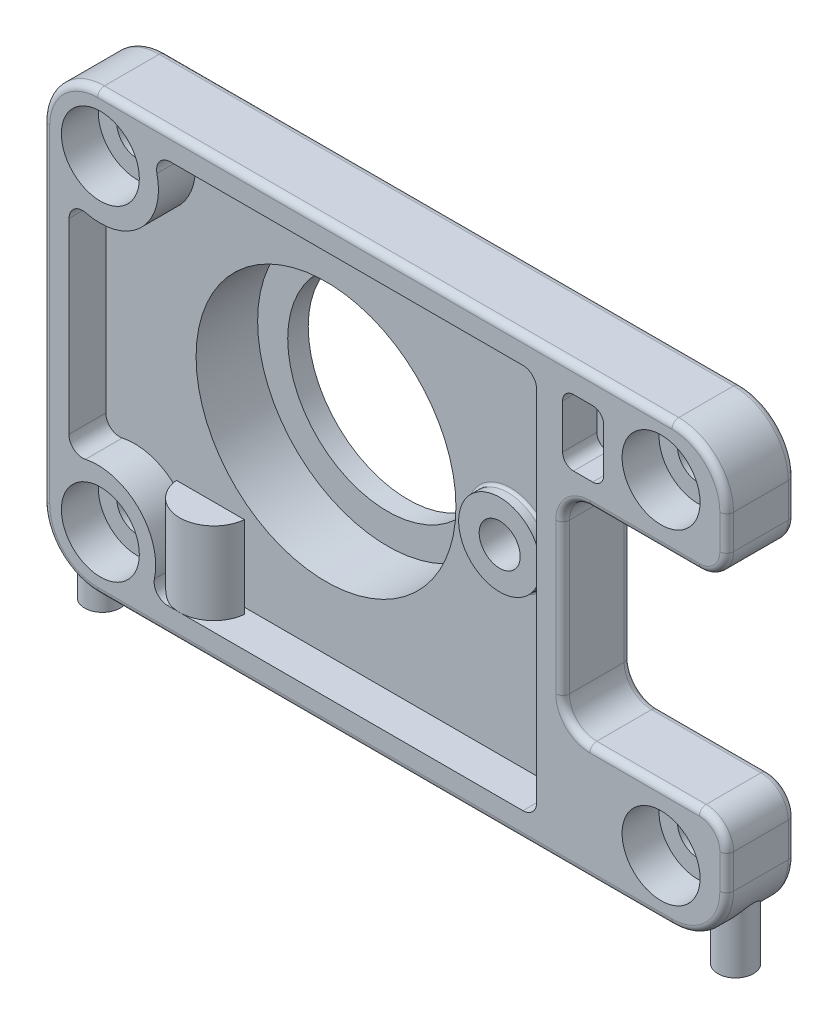
SolidWorks part; units mm, degrees
note: The reader was unsure of these and kept them because the rebuilt part matched: shared geometry of "草图16<2>", "草图16<3>".
ref_plane "前视基准面" through (0, 0, 0) normal (0, 0, 1) x (1, 0, 0)
ref_plane "上视基准面" through (0, 0, 0) normal (0, 1, 0) x (1, 0, 0)
ref_plane "右视基准面" through (0, 0, 0) normal (1, 0, 0) x (0, 0, -1)
sketch "草图1" plane through (0, 0, 0) normal (0, 0, 1) x (1, 0, 0)
  line L0 (0, 16) -> (50, 16) construction
  line L1 (0, 0) -> (50, 0)
  line L2 (0, 0) -> (0, 32)
  line L3 (0, 32) -> (50, 32)
  line L4 (50, 0) -> (50, 8.5)
  line L5 (50, 23.5) -> (38, 23.5)
  line L6 (38, 23.5) -> (38, 8.5)
  line L7 (50, 8.5) -> (38, 8.5)
  line L8 (50, 23.5) -> (50, 32)
  line L9 (4.2, 27.9) -> (5.7, 27.9) construction
  line L10 (4.2, 27.9) -> (46.7, 27.9) construction
  line L11 (4.2, 4.1) -> (50, 4.25) construction
  line L12 (25, 0) -> (25, 37.6238) construction
  circle A0 centre (4.2, 27.9) radius 1.5
  circle A1 centre (45.2, 27.9) radius 1.5
  circle A2 centre (45.2, 4.1) radius 1.5
  circle A3 centre (4.2, 4.1) radius 1.5
  circle A4 centre (18, 16) radius 9.5
  point P22 (38, 16)
  dimension "D3" = 3
  dimension "D10" = 18
  dimension "D11" = 19
  dimension "D1" = 50
  dimension "D2" = 32
  dimension "D6" = 4.2
  dimension "D8" = 23.8
  dimension "D12" = 8.5
  dimension "D13" = 12
  dimension "D14" = 41
  dimension "D4" = 2
  dimension "D5" = 2
extrude "凸台-拉伸1" add sketch "草图1" along normal blind 5
sketch "草图2" plane through (0, 0, 5) normal (0, 0, 1) x (1, 0, 0)
  line L0 (38, 8.5) -> (38, 23.5) construction
  line L1 (38, 25.2613) -> (41, 25.2613)
  line L2 (38, 25.2613) -> (38, 30.1)
  line L3 (36.1, 1.9) -> (36.1, 30.1)
  line L4 (7.6949, 1.9) -> (36.1, 1.9)
  line L5 (36.1, 30.1) -> (7.8363, 30.1)
  line L6 (38, 30.1) -> (41, 30.1)
  line L7 (41, 25.2613) -> (41, 30.1)
  line L8 (38, 6.74) -> (38, 1.9)
  line L9 (38, 1.9) -> (41, 1.9)
  line L10 (41, 1.9) -> (41, 6.74)
  line L11 (41, 6.74) -> (38, 6.74)
  line L24 (1.9124, 24.3182) -> (1.9, 7.6949)
  circle A0 centre (4.2, 27.9) radius 1.5 construction
  circle A1 centre (4.2, 27.9) radius 1.5 construction
  circle A2 centre (4.2, 4.1) radius 1.5 construction
  circle A3 centre (4.2, 4.1) radius 1.5 construction
  circle A4 centre (45.2, 27.9) radius 1.5 construction
  circle A5 centre (45.2, 27.9) radius 1.5 construction
  circle A6 centre (45.2, 4.1) radius 1.5 construction
  circle A7 centre (45.2, 4.1) radius 1.5 construction
  circle A8 centre (4.2, 27.9) radius 2.85
  circle A9 centre (4.2, 4.1) radius 2.85
  circle A10 centre (45.2, 4.1) radius 2.85
  circle A11 centre (45.2, 27.9) radius 2.85
  arc A12 (1.9124, 24.3182) -> (7.8363, 30.1) centre (4.2, 27.9) ccw
  circle A15 centre (4.2, 27.9) radius 4.25 construction
  arc A16 (7.6949, 1.9) -> (1.9, 7.6949) centre (4, 4) ccw
  circle M13 centre (45.2, 4.1) radius 1.5
  circle M14 centre (18, 16) radius 9.5
  circle M23 centre (4.2, 27.9) radius 1.5
  circle M24 centre (45.2, 27.9) radius 1.5
  circle M25 centre (4.2, 4.1) radius 1.5
  dimension "D4" = 3
  dimension "D6" = 4.9
  dimension "D1" = 4.8387
  dimension "D7" = 4.84
  dimension "D2" = 1.35
  dimension "D3" = 1.35
  dimension "D5" = 1.4
extrude "切除-拉伸1" cut sketch "草图2" against normal blind 2.7 contours A16 L4 L3 L5 A12 L24 M14 | M14 | A11 M24 | A10 M13 | A8 M23 | A9 M25
fillet "圆角1" radius 1 6 edges at (36.1, 1.9, 3.65) (7.8363, 30.1, 3.65) (1.9124, 24.3182, 3.65) (1.9, 7.6949, 3.65) (7.6949, 1.9, 3.65) (36.1, 30.1, 3.65)
fillet "圆角2" radius 4 4 edges at (0, 0, 2.5) (0, 32, 2.5) (50, 0, 2.5) (50, 32, 2.5)
fillet "圆角3" radius 2 4 edges at (38, 23.5, 2.5) (38, 8.5, 2.5) (50, 8.5, 2.5) (50, 23.5, 2.5)
sketch "草图3" plane through (0, 0, 0) normal (0, 0, -1) x (-1, 0, 0)
  circle A0 centre (-18, 16) radius 11.75
  circle A1 centre (-18, 16) radius 9.5 construction
  circle A2 centre (-18, 16) radius 9.5
  dimension "D1" = 23.5
extrude "凸台-拉伸2" add sketch "草图3" along normal blind 2.2
sketch "草图4" plane through (0, 0, -2.2) normal (0, 0, -1) x (-1, 0, 0)
  circle A0 centre (-18, 16) radius 11.75 construction
  circle A1 centre (-18, 16) radius 11.75
  circle A2 centre (-18, 16) radius 7.3
  dimension "D1" = 14.6
extrude "凸台-拉伸3" add sketch "草图4" along normal blind 1.5
fillet "圆角4" radius 0.5 1 edges at (6.25, 16, -3.7)
fillet "圆角5" radius 0.5 16 edges at (38.5858, 22.9142, 0) (38, 16, 0) (38.5858, 9.0858, 0) (44, 8.5, 0) (49.4142, 7.9142, 0) (50, 5.25, 0) (48.8284, 1.1716, 0) (25, 0, 0) (1.1716, 1.1716, 0) (0, 16, 0) (1.1716, 30.8284, 0) (25, 32, 0) (48.8284, 30.8284, 0) (50, 26.75, 0) (49.4142, 24.0858, 0) (44, 23.5, 0)
ref_plane "基准面1" through (0, -2.5, 0) normal (0, -1, 0) x (-1, 0, 0)
ref_plane "基准面2" through (25, 0, 0) normal (1, 0, 0) x (0, 0, -1)
sketch "草图5" plane through (0, -2.5, 0) normal (0, -1, 0) x (-1, 0, 0)
  line L0 (-50.15, -2.5) -> (-37.1404, -2.5) construction
  line L2 (-25, -5) -> (-25, 0) construction
  line L3 (-25, 2.2) -> (-25, -2.2) construction
  line L4 (-50, -5) -> (-46, -5) construction
  line L6 (-4, -5) -> (-46, -5) construction
  line L7 (-46, 0) -> (-4, 0) construction
  circle A0 centre (-48.15, -2.5) radius 1.3
  dimension "D1" = 2.6
  dimension "D3" = 2.5
  dimension "D2" = 23.15
extrude "凸台-拉伸5" add sketch "草图5" against normal up to surface (3.1269 mm away) up to face at (48.4142, 1.5858, 2.75)
mirror "镜向3" about plane through (25, 0, 0) normal (1, 0, 0) of "凸台-拉伸5"
sketch "草图8" plane through (0, 1.9, 0) normal (0, 1, 0) x (1, 0, 0)
  line L0 (9.1335, -5) -> (35.1, -5) construction
  line L1 (46, 0) -> (4, 0) construction
  line L2 (4, -5) -> (4, -0.5) construction
  line L4 (7.5125, -2.75) -> (12.4875, -2.75)
  line L5 (4, -5) -> (4, -0.5) construction
  line L6 (4, -2.75) -> (14.8659, -2.75) construction
  arc A0 (7.5125, -2.75) -> (12.4875, -2.75) centre (10, -2.5) ccw
  dimension "D1" = 10
extrude "凸台-拉伸6" add sketch "草图8" along normal blind 6
hole_wizard "M3 螺纹孔2" positions "草图10" profile "草图9" tap size "M3" standard "Gb"
sketch "草图10" plane through (0, 0, 0) normal (0, -1, 0) x (-1, 0, 0)
  line L4 (-24.85, -2.5) -> (-9.85, -2.5) construction
  line L5 (-25, 0) -> (-25, -5) construction
  line L6 (-4, 0) -> (-46, 0) construction
  line L7 (-46, -5) -> (-4, -5) construction
  point P10 (-9.85, -2.5)
  point P12 (-40.15, -2.5)
  dimension "D1" = 30.3
sketch "草图9" plane through (9.85, 0, 2.5) normal (1, 0, 0) x (0, 0, -1)
  line L0 (0, 0) -> (0, 6.7511)
  line L1 (0, 6.7511) -> (1.25, 6)
  line L2 (1.25, 6) -> (1.25, 0)
  line L5 (1.25, 0) -> (0, 0)
  line L10 (0, 6.7511) -> (-1.25, 6) construction
  line L11 (0, -6.35) -> (0, 107.95) construction
  dimension "螺纹孔钻头直径" = 2.5
  dimension "螺纹孔钻头深度" = 6
  dimension "导头角度" = 118
cosmetic thread "孔螺蚊线2" parameters "D1"=4, "D2"=3
cosmetic thread "孔螺蚊线3" parameters "D1"=4, "D2"=3
ref_plane "基准面3" through (0, 16, 0) normal (0, -1, 0) x (-1, 0, 0)
sketch "草图11" plane through (0, 32, 0) normal (0, 1, 0) x (1, 0, 0)
  line L2 (12.492, -2.3) -> (7.508, -2.3)
  arc A2 (7.508, -2.3) -> (12.492, -2.3) centre (10, -2.5) ccw
  dimension "D1" = 10
extrude "凸台-拉伸7" [suppressed] add sketch "草图11" against normal blind 8
hole_wizard "M3 螺纹孔3" [suppressed] positions "草图13" profile "草图12" tap size "M3" standard "Gb"
sketch "草图13" [suppressed] plane through (0, 32, 0) normal (0, 1, 0) x (1, 0, 0)
  arc A0 (7.508, -2.3) -> (12.492, -2.3) centre (10, -2.5) ccw construction
  arc A1 (7.508, -2.3) -> (12.492, -2.3) centre (10, -2.5) ccw construction
  point P1 (10, -2.5)
  point P6 (40, -2.5)
  dimension "D1" = 30
sketch "草图12" plane through (10, 32, 2.5) normal (1, 0, 0) x (0, 0, 1)
  line L0 (0, 0) -> (0, 6.2511)
  line L1 (0, 6.2511) -> (1.25, 5.5)
  line L2 (1.25, 5.5) -> (1.25, 0)
  line L5 (1.25, 0) -> (0, 0)
  line L10 (0, 6.2511) -> (-1.25, 5.5) construction
  line L11 (0, -6.35) -> (0, 107.95) construction
  dimension "螺纹孔钻头直径" = 2.5
  dimension "螺纹孔钻头深度" = 5.5
  dimension "导头角度" = 118
cosmetic thread "孔螺蚊线4" parameters "D1"=4, "D2"=3
cosmetic thread "孔螺蚊线5" parameters "D1"=4, "D2"=3
fillet "圆角6" radius 0.5 16 edges at (1.1716, 1.1716, 5) (0, 16, 5) (1.1716, 30.8284, 5) (25, 32, 5) (48.8284, 30.8284, 5) (50, 26.75, 5) (49.4142, 24.0858, 5) (44, 23.5, 5) (38.5858, 22.9142, 5) (38, 16, 5) (38.5858, 9.0858, 5) (44, 8.5, 5) (49.4142, 7.9142, 5) (50, 5.25, 5) (48.8284, 1.1716, 5) (25, 0, 5)
ref_plane "基准面4" through (0, 34.5, 0) normal (0, 1, 0) x (1, 0, 0)
sketch "草图14" plane through (0, 34.5, 0) normal (0, 1, 0) x (1, 0, 0)
  line L1 (0, -2.5) -> (5.731, -2.5) construction
  line L2 (0, -4.5) -> (0, -0.5) construction
  line L3 (25, -2.2) -> (25, 2.2) construction
  circle A0 centre (2, -2.5) radius 1.3
  dimension "D1" = 2.6
  dimension "D2" = 23
extrude "凸台-拉伸8" [suppressed] add sketch "草图14" against normal up to surface (3.0359 mm away)
mirror "镜向7" [suppressed] about plane through (25, 0, 0) normal (1, 0, 0)
sketch "草图15" plane through (0, 0, 5) normal (0, 0, 1) x (1, 0, 0)
  line L0 (41, 6.74) -> (38, 6.74) construction
  line L1 (38, 6.74) -> (38, 1.9) construction
  line L2 (38, 1.9) -> (41, 1.9) construction
  line L3 (41, 1.9) -> (41, 6.74) construction
  line L4 (38, 30.1) -> (41, 30.1) construction
  line L5 (38, 25.2613) -> (38, 30.1) construction
  line L6 (38, 25.2613) -> (41, 25.2613) construction
  line L7 (41, 25.2613) -> (41, 30.1) construction
  line L8 (41, 6.74) -> (38, 6.74)
  line L9 (38, 6.74) -> (38, 1.9)
  line L10 (38, 1.9) -> (41, 1.9)
  line L11 (41, 1.9) -> (41, 6.74)
  line L12 (38, 30.1) -> (41, 30.1)
  line L13 (38, 25.2613) -> (38, 30.1)
  line L14 (38, 25.2613) -> (41, 25.2613)
  line L15 (41, 25.2613) -> (41, 30.1)
extrude "切除-拉伸2" cut sketch "草图15" against normal blind 2.5 contours L14 L15 L12 L13
fillet "圆角7" radius 0.8 4 edges at (41, 30.1, 3.75) (38, 30.1, 3.75) (41, 25.2613, 3.75) (38, 25.2613, 3.75)
sketch "草图16" plane through (0, 0, 2.3) normal (0, 0, 1) x (1, 0, 0)
  line L0 (18, 16) -> (41.9863, 16) construction
  circle A0 centre (31.5, 16) radius 3
  circle A1 centre (31.5, 16) radius 1.5
  dimension "D1" = 6
  dimension "D3" = 1.5
  dimension "D2" = 13.5
extrude "凸台-拉伸9" add sketch "草图16" along normal blind 0.8
extrude "凸台-拉伸10" add sketch "草图16<2>" against normal blind 4 contours A0
sketch "草图16<2>" plane through (0, 0, 2.3) normal (0, 0, 1) x (1, 0, 0) same geometry as "草图16"
extrude "切除-拉伸3" cut sketch "草图16<3>" against normal blind 3.6 contours L0 A1 | A1 L0
sketch "草图16<3>" plane through (0, 0, 2.3) normal (0, 0, 1) x (1, 0, 0) same geometry as "草图16"
fillet "圆角8" radius 0.2 2 edges at (34.5, 16, 2.3) (34.5, 16, -1.7)
sketch "草图17" plane through (0, 0, 0) normal (0, 0, -1) x (-1, 0, 0)
  circle A0 centre (-45.2, 27.9) radius 2.85
  circle A1 centre (-4.2, 27.9) radius 2.85
  circle A2 centre (-45.2, 4.1) radius 2.85
  circle A3 centre (-4.2, 4.1) radius 2.85
  circle A4 centre (-45.2, 27.9) radius 1.5 construction
  circle A5 centre (-4.2, 27.9) radius 1.5 construction
  circle A6 centre (-4.2, 4.1) radius 1.5 construction
  circle A7 centre (-45.2, 4.1) radius 1.5 construction
  circle A8 centre (-45.2, 27.9) radius 1.5
  circle A9 centre (-4.2, 27.9) radius 1.5
  circle A10 centre (-4.2, 4.1) radius 1.5
  circle A11 centre (-45.2, 4.1) radius 1.5
  dimension "D1" = 5.7
  dimension "D2" = 5.7
  dimension "D3" = 5.7
  dimension "D4" = 5.7
extrude "切除-拉伸4" cut sketch "草图17" against normal blind 1
